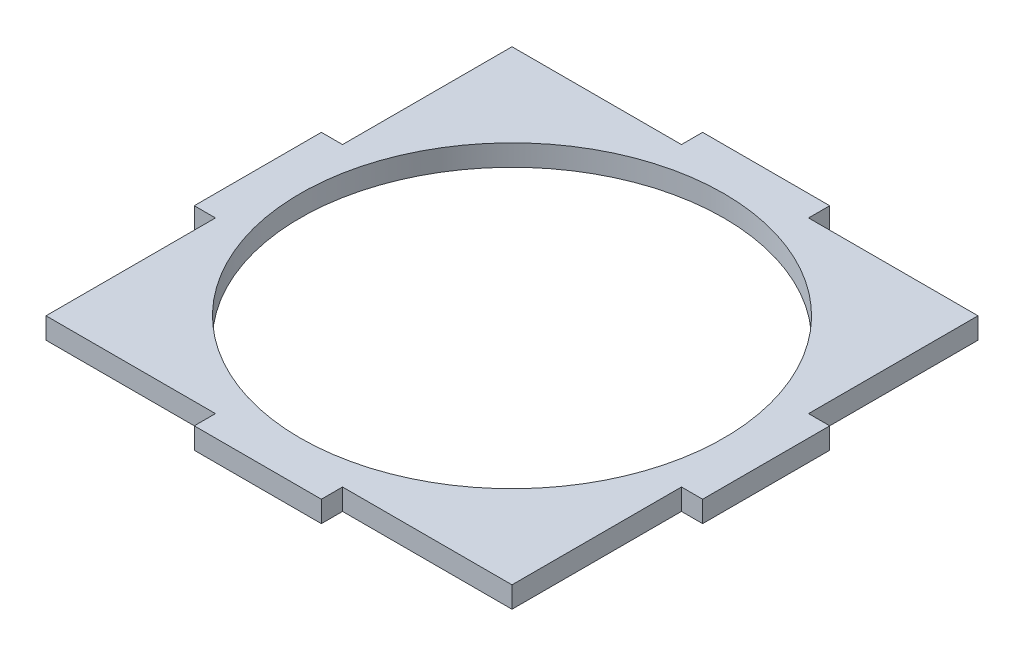
SolidWorks part; units mm, degrees
ref_plane "Front Plane" through (0, 0, 0) normal (0, 0, 1) x (1, 0, 0)
ref_plane "Top Plane" through (0, 0, 0) normal (0, 1, 0) x (1, 0, 0)
ref_plane "Right Plane" through (0, 0, 0) normal (1, 0, 0) x (0, 0, -1)
sketch "Sketch2" plane through (0, 0, 0) normal (0, 1, 0) x (1, 0, 0)
  line L0 (-19.05, -63.5) -> (-19.05, -76.2)
  line L1 (-69.85, -69.85) -> (69.85, -69.85)
  line L2 (-69.85, -69.85) -> (-69.85, 69.85)
  line L3 (-69.85, 69.85) -> (69.85, 69.85)
  line L4 (69.85, -69.85) -> (69.85, 69.85)
  line L5 (-69.85, -69.85) -> (69.85, 69.85) construction
  line L6 (-69.85, 69.85) -> (69.85, -69.85) construction
  line L7 (-63.5, -19.05) -> (-76.2, -19.05)
  line L8 (-63.5, -19.05) -> (-63.5, 19.05)
  line L9 (-63.5, 19.05) -> (-76.2, 19.05)
  line L10 (-76.2, -19.05) -> (-76.2, 19.05)
  line L11 (-63.5, -19.05) -> (-76.2, 19.05) construction
  line L12 (-63.5, 19.05) -> (-76.2, -19.05) construction
  line L13 (19.05, -63.5) -> (19.05, -76.2)
  line L14 (-19.05, -76.2) -> (19.05, -76.2)
  line L15 (63.5, -19.05) -> (76.2, -19.05)
  line L16 (63.5, 19.05) -> (76.2, 19.05)
  line L17 (76.2, 19.05) -> (76.2, -19.05)
  line L18 (19.05, 63.5) -> (19.05, 76.2)
  line L19 (19.05, 76.2) -> (-19.05, 76.2)
  line L20 (-19.05, 63.5) -> (-19.05, 76.2)
  circle A0 centre (0, 0) radius 63.5
  point P1 (0, 0)
  point P8 (-69.85, 0)
extrude "Boss-Extrude2" add sketch "Sketch2" along normal blind 6.35 contours A0 | L4 L3 L2 L1
ref_plane "Plane1" through (-69.85, 0, -69.85) normal (0, 0, -1) x (-1, 0, 0)
extrude "Boss-Extrude3" add sketch "Sketch2<4>" along normal blind 6.35 contours L10 L7 L2 L9 | L0 L14 L13 L1 | L17 L16 L4 L15 | L20 L3 L18 L19 region at (0, 0, 73.025) region at (-73.025, 0, 0) region at (73.025, 0, 0) region at (0, 0, -73.025)
sketch "Sketch2<4>" plane through (0, 0, 0) normal (0, 1, 0) x (1, 0, 0) same geometry as "Sketch2"
